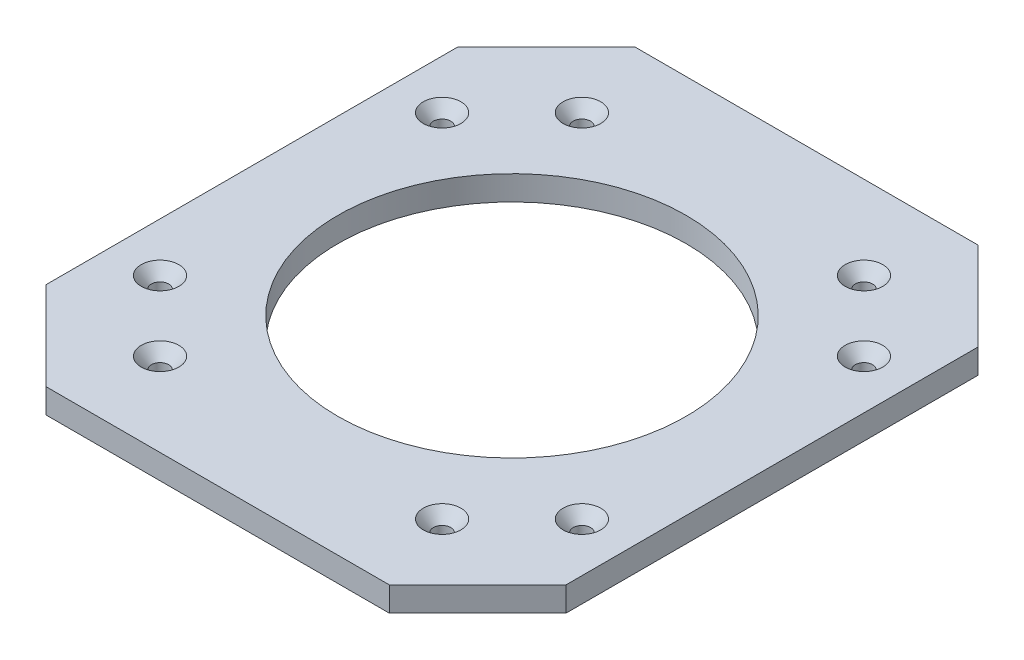
SolidWorks part; units mm, degrees
material "6061-T6 (SS)"
ref_plane "Front Plane" through (0, 0, 0) normal (0, 0, 1) x (1, 0, 0)
ref_plane "Top Plane" through (0, 0, 0) normal (0, 1, 0) x (1, 0, 0)
ref_plane "Right Plane" through (0, 0, 0) normal (1, 0, 0) x (0, 0, -1)
sketch "Sketch1" plane through (0, 0, 0) normal (0, 1, 0) x (1, 0, 0)
  line L0 (-67.31, 53.34) -> (-44.45, 76.2)
  line L1 (-44.45, -76.2) -> (44.45, -76.2)
  line L2 (-67.31, -53.34) -> (-67.31, 53.34)
  line L3 (-44.45, 76.2) -> (44.45, 76.2)
  line L4 (67.31, -53.34) -> (67.31, 53.34)
  line L5 (-85.725, -85.725) -> (85.725, 85.725) construction
  line L6 (-85.725, 85.725) -> (85.725, -85.725) construction
  line L7 (44.45, 76.2) -> (67.31, 53.34)
  line L8 (67.31, -53.34) -> (44.45, -76.2)
  line L9 (-67.31, -53.34) -> (-44.45, -76.2)
  circle A0 centre (0, 0) radius 54.61 construction
  point P0 (0, 0)
  point P16 (-67.31, 0)
  point P18 (0, 76.2)
  dimension "D4" = 109.22
  dimension "D1" = 171.45
  dimension "D2" = 171.45
  dimension "D3" = 88.9
  dimension "D5" = 152.4
  dimension "D6" = 12.7
extrude "Boss-Extrude1" add sketch "Sketch1" along normal blind 6.35
hole_wizard "CSK for #8 Flat Head Machine Screw1" positions "Sketch3" profile "Sketch2" countersink size "#8" standard "ANSI Inch" end condition through all
sketch "Sketch3" plane through (0, 6.35, 0) normal (0, 1, 0) x (-1, 0, 0)
  line L0 (-36.5125, -54.61) -> (0, 0) construction
  line L1 (0, 0) -> (36.5125, -54.61) construction
  line L2 (36.5125, -54.61) -> (-36.5125, -54.61) construction
  line L5 (-54.61, -36.5125) -> (-54.61, 36.5125) construction
  line L8 (0, 0) -> (-54.61, -36.5125) construction
  line L11 (0, 0) -> (-54.61, 36.5125) construction
  line L14 (0, 0) -> (-36.5125, 54.61) construction
  line L15 (-36.5125, 54.61) -> (36.5125, 54.61) construction
  line L16 (36.5125, 54.61) -> (0, 0) construction
  line L17 (0, 0) -> (54.61, 36.5125) construction
  line L18 (54.61, 36.5125) -> (54.61, -36.5125) construction
  line L19 (54.61, -36.5125) -> (0, 0) construction
  point P0 (36.5125, -54.61)
  point P1 (-36.5125, -54.61)
  point P19 (36.5125, 54.61)
  point P21 (-36.5125, 54.61)
  point P23 (-54.61, -36.5125)
  point P25 (-54.61, 36.5125)
  point P27 (54.61, 36.5125)
  point P29 (54.61, -36.5125)
  dimension "D1" = 73.025
  dimension "D3" = 109.22
sketch "Sketch2" plane through (-36.5125, 6.35, -54.61) normal (1, 0, 0) x (0, 0, 1)
  line L0 (0, 0) -> (0, 6.35)
  line L1 (0, 6.35) -> (2.2479, 6.35)
  line L2 (2.2479, 6.35) -> (2.2479, 3.0265)
  line L3 (2.2479, 3.0265) -> (4.8788, 0)
  line L5 (4.8788, 0) -> (0, 0)
  line L6 (-2.2479, 3.0265) -> (-4.8788, 0) construction
  line L11 (0, -6.35) -> (0, 107.95) construction
  dimension "Thru Hole Dia." = 4.4958
  dimension "Thru Hole Depth" = 6.35
  dimension "Near C'Sink Dia." = 9.7576
  dimension "Near C'Sink Angle" = 82
ref_axis "Axis1" through (0, 0, 0) along (0, 1, 0)
pattern_circular "CirPattern1" count 2 over 360 about axis through (0, 0, 0) along (0, 1, 0) of "CSK for #8 Flat Head Machine Screw1"
sketch "Sketch4" plane through (0, 6.35, 0) normal (0, 1, 0) x (1, 0, 0)
  circle A0 centre (0, 0) radius 45.085
  dimension "D1" = 90.17
extrude "Cut-Extrude1" cut sketch "Sketch4" against normal through all
